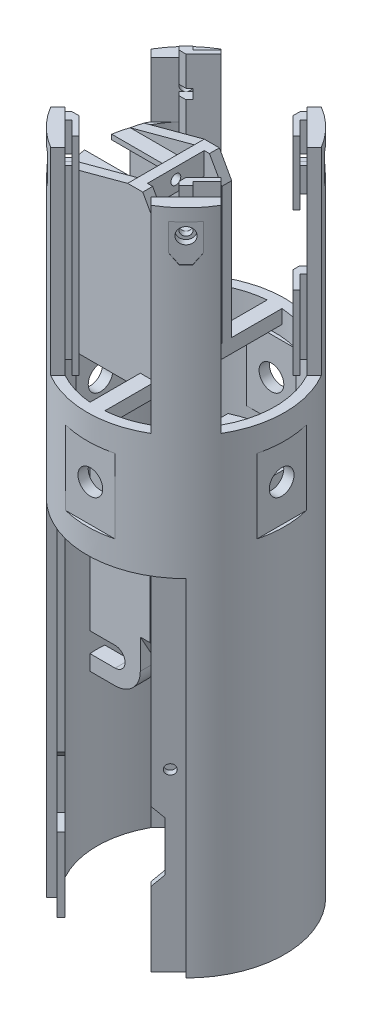
SolidWorks part; units mm, degrees
ref_plane "前视基准面" through (0, 0, 0) normal (0, 0, 1) x (1, 0, 0)
ref_plane "上视基准面" through (0, 0, 0) normal (0, 1, 0) x (1, 0, 0)
ref_plane "右视基准面" through (0, 0, 0) normal (1, 0, 0) x (0, 0, -1)
other "Configuration Table"
sketch "草图1" plane through (0, 0, 0) normal (0, 1, 0) x (1, 0, 0)
  circle A0 centre (0, 0) radius 20
  circle A1 centre (0, 0) radius 18
  dimension "D1" = 40
  dimension "D2" = 36
extrude "凸台-拉伸1" add sketch "草图1" along normal blind 25
sketch "草图2" plane through (0, 0, 0) normal (0, 1, 0) x (1, 0, 0)
  line L0 (-1000, 0) -> (49000, 0) construction
  line L1 (-17.9374, 1.5) -> (-17.9374, -1.5) construction
  line L2 (-17.9374, 1.5) -> (17.9374, 1.5)
  line L3 (-17.9374, -1.5) -> (17.9374, -1.5)
  circle A0 centre (0, 0) radius 18 construction
  arc A2 (-17.9374, 1.5) -> (-17.9374, -1.5) centre (0, 0) ccw
  arc A3 (17.9374, -1.5) -> (17.9374, 1.5) centre (0, 0) ccw
  point P8 (-17.9374, 0)
  dimension "D1" = 3
extrude "凸台-拉伸2" add sketch "草图2" along normal blind 2.8 from surface starting at face at (0, 0, 20)
sketch "草图3" plane through (0, 0, 0) normal (0, 1, 0) x (1, 0, 0)
  line L0 (0, -1000) -> (0, 49000) construction
  line L2 (7.75, 16.2462) -> (7.75, -1.5)
  line L3 (17.9374, -1.5) -> (-17.9374, -1.5) construction
  line L4 (7.75, -1.5) -> (-7.75, -1.5)
  line L5 (-7.75, -1.5) -> (-7.75, 16.2462)
  arc A0 (7.75, 16.2462) -> (-7.75, 16.2462) centre (0, 0) ccw
  point P9 (0, 16.2462)
  dimension "D1" = 15.5
  dimension "D2" = 15.5
  dimension "D3" = 17.7462
extrude "凸台-拉伸3" add sketch "草图3" along normal up to surface (2.8 mm away) up to face at (0, 2.8, 0)
sketch "草图4" plane through (0, 0, 0) normal (0, 1, 0) x (1, 0, 0)
  line L0 (7.75, 16.2462) -> (7.75, 2.0569)
  line L1 (-7.75, 16.2462) -> (-7.75, 2.0569)
  line L2 (5.75, 17.0569) -> (5.75, 4.0569)
  line L3 (-5.75, 17.0569) -> (-5.75, 4.0569)
  line L4 (5.75, 4.0569) -> (-5.75, 4.0569)
  line L5 (5.75, 2.0569) -> (-5.75, 2.0569)
  line L6 (-7.75, 2.0569) -> (-7.75, -1.5)
  line L7 (17.9374, -1.5) -> (-17.9374, -1.5) construction
  line L8 (-7.75, -1.5) -> (-5.75, -1.5)
  line L9 (-5.75, -1.5) -> (-5.75, 2.0569)
  line L10 (5.75, 2.0569) -> (5.75, -1.5)
  line L11 (5.75, -1.5) -> (7.75, -1.5)
  line L12 (7.75, -1.5) -> (7.75, 2.0569)
  arc A0 (7.75, 16.2462) -> (5.75, 17.0569) centre (0, 0) ccw
  arc A1 (-5.75, 17.0569) -> (-7.75, 16.2462) centre (0, 0) ccw
  dimension "D1" = 2
  dimension "D2" = 2
  dimension "D3" = 13
  dimension "D4" = 2
extrude "凸台-拉伸4" add sketch "草图4" against normal blind 32 from surface starting at face at (-11.8011, 0, -6.8681)
sketch "草图5" plane through (0, 0, 0) normal (0, 0, 1) x (1, 0, 0)
  line L0 (5.75, 0) -> (-5.75, -32) construction
  line L1 (5.75, -32) -> (-5.75, 0) construction
  line L2 (0, -2.2) -> (0, -29.8) construction
  line L3 (-5.75, -4.5) -> (5.75, -4.5)
  line L4 (-5.75, -4.5) -> (-5.75, -27.5)
  line L5 (-5.75, -27.5) -> (5.75, -27.5)
  line L6 (5.75, -4.5) -> (5.75, -27.5)
  line L7 (-5.75, -4.5) -> (5.75, -27.5) construction
  line L8 (-5.75, -27.5) -> (5.75, -4.5) construction
  circle A0 centre (0, -2.2) radius 1
  circle A1 centre (0, -29.8) radius 1
  point P8 (0, -16)
  point P17 (0, -16)
  dimension "D4" = 2
  dimension "D5" = 2
  dimension "D1" = 23
  dimension "D2" = 11.5
  dimension "D3" = 27.6
extrude "切除-拉伸1" cut sketch "草图5" against normal blind 32
sketch "草图6" plane through (0, 0, 0) normal (0, 1, 0) x (1, 0, 0)
  line L0 (5.75, 17.0569) -> (5.75, 4.0569)
  line L1 (-5.75, 4.0569) -> (5.75, 4.0569) construction
  line L2 (5.75, 4.0569) -> (5.75, 17.0569) construction
  line L3 (2.75, 4.0569) -> (2.75, 17.7887)
  line L4 (-5.75, 17.0569) -> (-5.75, 4.0569)
  line L5 (-5.75, 4.0569) -> (5.75, 4.0569) construction
  line L6 (-2.75, 4.0569) -> (-2.75, 17.7887)
  line L7 (2.75, 4.0569) -> (5.75, 4.0569)
  line L8 (-5.75, 4.0569) -> (-2.75, 4.0569)
  arc A0 (5.75, 17.0569) -> (2.75, 17.7887) centre (0, 0) ccw
  arc A1 (-2.75, 17.7887) -> (-5.75, 17.0569) centre (0, 0) ccw
  dimension "D1" = 3
  dimension "D2" = 3
extrude "凸台-拉伸5" add sketch "草图6" against normal blind 1 from surface starting at face at (0, -27.5, -3.0569)
sketch "草图7" plane through (0, 0, 0) normal (0, 1, 0) x (1, 0, 0)
  line L3 (2.75, 17.7887) -> (2.75, 4.0569)
  line L4 (5.75, 4.0569) -> (5.75, 17.0569)
  line L5 (2.75, 4.0569) -> (5.75, 4.0569)
  line L6 (2.75, 17.7887) -> (2.75, 4.0569)
  line L7 (5.75, 4.0569) -> (5.75, 17.0569)
  line L8 (2.75, 4.0569) -> (5.75, 4.0569)
  line L9 (-5.75, 17.0569) -> (-5.75, 4.0569)
  line L10 (-2.75, 4.0569) -> (-2.75, 17.7887)
  line L11 (-5.75, 4.0569) -> (-2.75, 4.0569)
  line L12 (-5.75, 17.0569) -> (-5.75, 4.0569)
  line L13 (-2.75, 4.0569) -> (-2.75, 17.7887)
  line L14 (-5.75, 4.0569) -> (-2.75, 4.0569)
  arc A1 (5.75, 17.0569) -> (2.75, 17.7887) centre (0, 0) ccw
  arc A2 (5.75, 17.0569) -> (2.75, 17.7887) centre (0, 0) ccw
  arc A3 (-2.75, 17.7887) -> (-5.75, 17.0569) centre (0, 0) ccw
  arc A4 (-2.75, 17.7887) -> (-5.75, 17.0569) centre (0, 0) ccw
  dimension "D1" = 0
  dimension "D2" = 0
extrude "凸台-拉伸6" add sketch "草图7" along normal blind 1 from surface starting at face at (0, -4.5, -3.0569)
sketch "草图8" plane through (0, 0, 0) normal (0, 1, 0) x (1, 0, 0)
  line L0 (-2.75, 17.7887) -> (-2.75, 4.0569) construction
  line L1 (2.75, 4.0569) -> (2.75, 17.7887) construction
  line L2 (-2.75, 17.7887) -> (-2.75, 4.0569)
  line L3 (2.75, 4.0569) -> (2.75, 17.7887)
  line L4 (2.75, 4.0569) -> (-2.75, 4.0569)
  arc A0 (2.75, 17.7887) -> (-2.75, 17.7887) centre (0, 0) ccw
extrude "切除-拉伸2" cut sketch "草图8" along normal up to surface (2.8 mm away) from surface up to face at (0, 2.8, -4.6558) starting at face at (0, 0, -0.2784)
sketch "草图9" plane through (0, 0, 0) normal (1, 0, 0) x (0, 0, -1)
  line L0 (-1.5, -32) -> (-1.5, -27.5)
  line L1 (-1.5, -32) -> (-1.5, 0) construction
  line L2 (-1.5, -32) -> (1, -32)
  line L3 (-1.5, -32) -> (16.2462, -32) construction
  line L4 (1, -32) -> (-1.5, -27.5)
  line L5 (17.0569, -32) -> (4.0569, -32)
  line L6 (4.0569, -32) -> (17.0569, -28.5)
  line L7 (17.0569, -28.5) -> (17.0569, -32)
  dimension "D1" = 4.5
  dimension "D2" = 13
  dimension "D3" = 2.5
extrude "切除-拉伸3" cut sketch "草图9" against normal through all and the other way through all contours L7 L5 L6 | L4 L0 L2
sketch "草图10" plane through (0, 0, 0) normal (0, 1, 0) x (1, 0, 0)
  line L0 (0, -1000) -> (0, 49000) construction
  line L1 (-1.5, 17.9374) -> (1.5, 17.9374) construction
  line L2 (-1.5, 17.9374) -> (-1.5, -17.9374)
  line L3 (1.5, 17.9374) -> (1.5, -17.9374)
  arc A0 (1.5, 17.9374) -> (-1.5, 17.9374) centre (0, 0) ccw
  arc A1 (-1.5, -17.9374) -> (1.5, -17.9374) centre (0, 0) ccw
  point P9 (0, 17.9374)
  dimension "D1" = 3
extrude "凸台-拉伸7" add sketch "草图10" against normal blind 2.8 from surface starting at face at (0, 25, 20)
sketch "草图12" plane through (0, 0, 0) normal (0, 1, 0) x (1, 0, 0)
  line L0 (-1000, 0) -> (49000, 0) construction
  line L1 (-16.2462, -7.75) -> (-16.2462, 7.75) construction
  line L2 (-16.2462, 7.75) -> (1.5, 7.75)
  line L3 (1.5, 17.9374) -> (1.5, -17.9374) construction
  line L4 (1.5, 7.75) -> (1.5, -7.75)
  line L5 (1.5, -7.75) -> (-16.2462, -7.75)
  arc A0 (-16.2462, 7.75) -> (-16.2462, -7.75) centre (0, 0) ccw
  point P9 (-16.2462, 0)
  dimension "D1" = 15.5
extrude "凸台-拉伸8" add sketch "草图12" against normal up to surface (-22.2 mm away) from surface up to face at (0, 22.2, 0) starting at face at (9.75, 25, 0)
sketch "草图13" plane through (0, 0, 0) normal (0, 1, 0) x (1, 0, 0)
  line L0 (-1000, 0) -> (49000, 0) construction
  line L1 (-16.2462, 7.75) -> (-16.2462, -7.75) construction
  line L2 (-16.2462, 7.75) -> (1.5, 7.75)
  line L3 (1.5, 17.9374) -> (1.5, -17.9374) construction
  line L4 (1.5, 7.75) -> (1.5, 5.75)
  line L5 (1.5, 5.75) -> (-2.0569, 5.75)
  line L6 (-16.2462, -7.75) -> (1.5, -7.75)
  line L7 (1.5, -7.75) -> (1.5, -5.75)
  line L8 (1.5, -5.75) -> (-2.0569, -5.75)
  line L9 (-4.0569, 5.75) -> (-4.0569, -5.75)
  line L10 (-2.0569, 5.75) -> (-2.0569, -5.75)
  line L11 (-4.0569, 5.75) -> (-17.0569, 5.75)
  line L12 (-4.0569, -5.75) -> (-17.0569, -5.75)
  arc A0 (-16.2462, 7.75) -> (-17.0569, 5.75) centre (0, 0) ccw
  arc A1 (-17.0569, -5.75) -> (-16.2462, -7.75) centre (0, 0) ccw
  point P9 (-16.2462, 0)
  point P18 (-7.3731, 7.75)
  dimension "D1" = 15.5
  dimension "D2" = 2
  dimension "D3" = 2
  dimension "D4" = 2
  dimension "D5" = 13
extrude "凸台-拉伸9" add sketch "草图13" along normal blind 32 from surface starting at face at (9.75, 25, 0)
sketch "草图14" plane through (0, 0, 0) normal (1, 0, 0) x (0, 0, -1)
  line L0 (5.75, 57) -> (-5.75, 25) construction
  line L1 (5.75, 25) -> (-5.75, 57) construction
  line L2 (0, 54.8) -> (0, 27.2) construction
  line L3 (-5.75, 52.5) -> (5.75, 52.5)
  line L4 (-5.75, 52.5) -> (-5.75, 29.5)
  line L5 (-5.75, 29.5) -> (5.75, 29.5)
  line L6 (5.75, 52.5) -> (5.75, 29.5)
  line L7 (-5.75, 52.5) -> (5.75, 29.5) construction
  line L8 (-5.75, 29.5) -> (5.75, 52.5) construction
  circle A0 centre (0, 54.8) radius 1
  circle A1 centre (0, 27.2) radius 1
  point P8 (0, 41)
  point P17 (0, 41)
  dimension "D4" = 2
  dimension "D5" = 2
  dimension "D1" = 23
  dimension "D2" = 11.5
  dimension "D3" = 27.6
extrude "切除-拉伸4" cut sketch "草图14" against normal blind 32
sketch "草图15" plane through (0, 0, 0) normal (0, 1, 0) x (1, 0, 0)
  line L0 (-17.0569, 5.75) -> (-4.0569, 5.75)
  line L1 (-4.0569, -5.75) -> (-4.0569, 5.75) construction
  line L2 (-4.0569, -5.75) -> (-4.0569, 5.75) construction
  line L3 (-4.0569, 5.75) -> (-4.0569, 2.75)
  line L4 (-4.0569, 2.75) -> (-17.7887, 2.75)
  line L5 (-4.0569, -5.75) -> (-4.0569, -2.75)
  line L6 (-4.0569, -2.75) -> (-17.7887, -2.75)
  line L7 (-4.0569, -5.75) -> (-17.0569, -5.75)
  line L8 (-17.0569, -5.75) -> (-4.0569, -5.75) construction
  arc A0 (-17.7887, -2.75) -> (-17.0569, -5.75) centre (0, 0) ccw
  arc A1 (-17.0569, 5.75) -> (-17.7887, 2.75) centre (0, 0) ccw
  dimension "D1" = 3
  dimension "D2" = 3
extrude "凸台-拉伸10" add sketch "草图15" against normal blind 1 from surface starting at face at (-3.0569, 29.5, 0)
sketch "草图16" plane through (0, 0, 0) normal (0, 1, 0) x (1, 0, 0)
  line L0 (-4.0569, 5.75) -> (-4.0569, 2.75)
  line L1 (-4.0569, -2.75) -> (-4.0569, -5.75)
  line L2 (-17.0569, -5.75) -> (-2.0569, -5.75) construction
  line L3 (-4.0569, -5.75) -> (-4.0569, 5.75) construction
  line L4 (-17.7887, 2.75) -> (-4.0569, 2.75) construction
  line L5 (-17.7887, 2.75) -> (-4.0569, 2.75)
  line L6 (-4.0569, -2.75) -> (-17.7887, -2.75) construction
  line L7 (-4.0569, -2.75) -> (-17.7887, -2.75)
  line L8 (-4.0569, 5.75) -> (-17.0569, 5.75)
  line L9 (-4.0569, -5.75) -> (-17.0569, -5.75)
  arc A0 (-17.7887, -2.75) -> (-17.0569, -5.75) centre (0, 0) ccw construction
  arc A1 (-17.7887, -2.75) -> (-17.0569, -5.75) centre (0, 0) ccw
  arc A2 (-17.0569, 5.75) -> (-17.7887, 2.75) centre (0, 0) ccw construction
  arc A3 (-17.0569, 5.75) -> (-17.7887, 2.75) centre (0, 0) ccw
extrude "凸台-拉伸11" add sketch "草图16" along normal blind 1 from surface contours L8 A3 L5 L0 | L7 A1 L9 L1 region at (-10.7643, 0, -4.2364) region at (-10.7643, 0, 4.2364) starting at face at (-3.0569, 52.5, 0)
sketch "草图17" plane through (0, 0, 0) normal (0, 1, 0) x (1, 0, 0)
  line L0 (-4.0569, -5.75) -> (-4.0569, 5.75) construction
  line L1 (-17.7887, -2.75) -> (-4.0569, -2.75) construction
  line L2 (-4.0569, 2.75) -> (-17.7887, 2.75) construction
  line L3 (-4.0569, -2.75) -> (-4.0569, 2.75)
  line L4 (-17.7887, -2.75) -> (-4.0569, -2.75)
  line L5 (-4.0569, 2.75) -> (-17.7887, 2.75)
  arc A0 (-17.7887, 2.75) -> (-17.7887, -2.75) centre (0, 0) ccw
extrude "切除-拉伸5" cut sketch "草图17" against normal up to surface (-22.2 mm away) from surface up to face at (-4.6558, 22.2, 0) starting at face at (0, 25, 20)
sketch "草图18" plane through (0, 0, 0) normal (0, 0, 1) x (1, 0, 0)
  line L0 (1.5, 57) -> (1.5, 52.5)
  line L1 (1.5, 57) -> (1.5, 25) construction
  line L2 (1.5, 52.5) -> (-1, 57)
  line L3 (1.5, 57) -> (-16.2462, 57) construction
  line L4 (-1, 57) -> (1.5, 57)
  line L5 (-17.0569, 53.5) -> (-4.0569, 57)
  line L6 (-4.0569, 57) -> (-17.0569, 57)
  line L7 (-17.0569, 57) -> (-17.0569, 53.5)
  dimension "D1" = 13
  dimension "D2" = 4.5
  dimension "D3" = 2.5
extrude "切除-拉伸6" cut sketch "草图18" against normal through all and the other way through all
sketch "草图19" plane through (0, 0, 0) normal (0, 0, 1) x (1, 0, 0)
  line L0 (20, 25) -> (-20, 0) construction
  line L1 (-20, 25) -> (20, 0) construction
  circle A0 centre (0, 12.5) radius 2.5
  dimension "D1" = 5
sketch "草图20" plane through (0, 0, 0) normal (1, 0, 0) x (0, 0, -1)
  line L0 (20, 25) -> (-20, 0) construction
  line L1 (-20, 25) -> (20, 0) construction
  circle A0 centre (0, 12.5) radius 2.5
  dimension "D1" = 5
sketch "草图21" plane through (0, 0, 0) normal (0, 1, 0) x (1, 0, 0)
  line L0 (0, -1000) -> (0, 49000) construction
  line L1 (-1000, 0) -> (49000, 0) construction
  line L2 (-17.2916, -5) -> (-17.2916, 5)
  line L3 (17.2916, -5) -> (17.2916, 5)
  line L4 (-5, 17.2916) -> (5, 17.2916)
  line L5 (-5, -17.2916) -> (5, -17.2916)
  arc A0 (-17.2916, 5) -> (-17.2916, -5) centre (0, 0) ccw
  arc A1 (17.2916, -5) -> (17.2916, 5) centre (0, 0) ccw
  arc A2 (5, 17.2916) -> (-5, 17.2916) centre (0, 0) ccw
  arc A3 (-5, -17.2916) -> (5, -17.2916) centre (0, 0) ccw
  point P11 (-17.2916, 0)
  point P16 (0, 17.2916)
  dimension "D1" = 10
  dimension "D2" = 10
extrude "凸台-拉伸12" add sketch "草图21" along normal blind 15 from offset 5
sketch "草图22" plane through (0, 0, 0) normal (0, 1, 0) x (1, 0, 0)
  line L0 (-1000, 0) -> (49000, 0) construction
  line L1 (0, -1000) -> (0, 49000) construction
  line L2 (-5, 19.3649) -> (5, 19.3649)
  line L3 (-19.3649, -5) -> (-19.3649, 5)
  line L4 (19.3649, -5) -> (19.3649, 5)
  line L5 (-5, -19.3649) -> (5, -19.3649)
  arc A0 (-19.3649, 5) -> (-19.3649, -5) centre (0, 0) ccw
  arc A1 (5, 19.3649) -> (-5, 19.3649) centre (0, 0) ccw
  arc A2 (19.3649, -5) -> (19.3649, 5) centre (0, 0) ccw
  arc A3 (-5, -19.3649) -> (5, -19.3649) centre (0, 0) ccw
  point P10 (0, 19.3649)
  point P13 (-19.3649, 0)
  dimension "D1" = 40
  dimension "D2" = 10
  dimension "D3" = 10
extrude "切除-拉伸9" cut sketch "草图22" along normal blind 15 from offset 5
extrude "切除-拉伸10" cut sketch "草图19" against normal through all and the other way through all
extrude "切除-拉伸11" cut sketch "草图20" against normal through all and the other way through all
sketch "草图24" plane through (0, 0, 0) normal (0, 1, 0) x (1, 0, 0)
  circle A0 centre (0, 0) radius 20
  circle A1 centre (0, 0) radius 18
  dimension "D1" = 40
extrude "凸台-拉伸14" add sketch "草图24" against normal blind 70
sketch "草图27" plane through (0, 0, 0) normal (0, 1, 0) x (1, 0, 0)
  line L0 (-707.1068, -707.1068) -> (34648.2323, 34648.2323) construction
  line L1 (707.1068, -707.1068) -> (-34648.2323, 34648.2323) construction
  line L2 (-14.1421, -14.1421) -> (-12.7279, -12.7279)
  line L3 (14.1421, -14.1421) -> (12.7279, -12.7279)
  line L4 (-12.7279, 12.7279) -> (-14.1421, 14.1421)
  line L5 (12.7279, 12.7279) -> (14.1421, 14.1421)
  circle A0 centre (0, 0) radius 20 construction
  arc A1 (-14.1421, -14.1421) -> (14.1421, -14.1421) centre (0, 0) ccw
  circle A2 centre (0, 0) radius 18 construction
  arc A3 (-12.7279, -12.7279) -> (12.7279, -12.7279) centre (0, 0) ccw
  arc A4 (14.1421, 14.1421) -> (-14.1421, 14.1421) centre (0, 0) ccw
  arc A5 (12.7279, 12.7279) -> (-12.7279, 12.7279) centre (0, 0) ccw
extrude "切除-拉伸13" cut sketch "草图27" along normal up to surface from surface up to face at (0, 0, -0.2784) starting at face at (0, -70, 18)
sketch "草图28" plane through (0, 0, 0) normal (0, 1, 0) x (1, 0, 0)
  line L3 (-7.75, 1.5) -> (-17.9374, 1.5)
  line L4 (-7.75, -1.5) -> (-7.75, 1.5)
  line L5 (-17.9374, -1.5) -> (-7.75, -1.5)
  line L6 (-7.75, 1.5) -> (-17.9374, 1.5)
  line L7 (-7.75, -1.5) -> (-7.75, 1.5)
  line L8 (-17.9374, -1.5) -> (-7.75, -1.5)
  line L9 (7.75, -1.5) -> (17.9374, -1.5)
  line L10 (7.75, 1.5) -> (7.75, -1.5)
  line L11 (17.9374, 1.5) -> (7.75, 1.5)
  line L12 (7.75, -1.5) -> (17.9374, -1.5)
  line L13 (7.75, 1.5) -> (7.75, -1.5)
  line L14 (17.9374, 1.5) -> (7.75, 1.5)
  arc A0 (-12.7279, 12.7279) -> (-12.7279, -12.7279) centre (0, 0) ccw construction
  arc A1 (-17.9374, 1.5) -> (-17.9374, -1.5) centre (0, 0) ccw
  arc A2 (-17.9374, 1.5) -> (-17.9374, -1.5) centre (0, 0) ccw
  arc A3 (-17.9374, 1.5) -> (-17.9374, -1.5) centre (0, 0) ccw
  arc A4 (12.7279, -12.7279) -> (12.7279, 12.7279) centre (0, 0) ccw construction
  arc A5 (17.9374, -1.5) -> (17.9374, 1.5) centre (0, 0) ccw
  arc A7 (17.9374, -1.5) -> (17.9374, 1.5) centre (0, 0) ccw
  arc A8 (17.9374, -1.5) -> (17.9374, 1.5) centre (0, 0) ccw
  dimension "D1" = 0
  dimension "D2" = 0
extrude "凸台-拉伸16" add sketch "草图28" against normal up to vertex (27.5 mm away) contours L12 A5 L14 L13 | L6 A2 L8 L7 region at (-12.8646, 0, 0) region at (12.8646, 0, 0) up to point (-7.75, -27.5, 1.5)
sketch "草图32" plane through (0, 0, 0) normal (0, 1, 0) x (1, 0, 0)
  line L0 (-1000, 0) -> (49000, 0) construction
  line L1 (0, -1000) -> (0, 49000) construction
  line L2 (-707.1068, -707.1068) -> (34648.2323, 34648.2323) construction
  line L3 (707.1068, -707.1068) -> (-34648.2323, 34648.2323) construction
  line L4 (-15.7626, -8.6915) -> (-8.6915, -15.7626)
  line L8 (16.6111, -9.54) -> (9.54, -16.6111)
  line L9 (-16.6111, -9.54) -> (-9.54, -16.6111)
  line L10 (-16.6111, -9.54) -> (-15.7626, -8.6915)
  line L11 (-9.54, -16.6111) -> (-8.6915, -15.7626)
  line L12 (16.6111, -9.54) -> (15.7626, -8.6915)
  line L13 (15.7626, -8.6915) -> (8.6915, -15.7626)
  line L14 (9.54, -16.6111) -> (8.6915, -15.7626)
  line L15 (16.6111, 9.54) -> (15.7626, 8.6915)
  line L16 (15.7626, 8.6915) -> (8.6915, 15.7626)
  line L17 (9.54, 16.6111) -> (8.6915, 15.7626)
  line L18 (16.6111, 9.54) -> (9.54, 16.6111)
  line L19 (-16.6111, 9.54) -> (-9.54, 16.6111)
  line L20 (-16.6111, 9.54) -> (-15.7626, 8.6915)
  line L21 (-15.7626, 8.6915) -> (-8.6915, 15.7626)
  line L22 (-9.54, 16.6111) -> (-8.6915, 15.7626)
  circle A0 centre (0, 0) radius 18 construction
  point P15 (-12.227, -12.227)
  point P19 (-12.7279, -12.7279)
  point P22 (-13.0755, -13.0755)
  dimension "D1" = 10
  dimension "D2" = 10
  dimension "D3" = 1.2
extrude "凸台-拉伸30" add sketch "草图32" against normal up to surface (70 mm away) from surface contours L9 L11 L4 L10 | L19 L22 L21 L20 | L18 L17 L16 L15 | L8 L14 L13 L12 up to face at (-16.2175, -70, 0) starting at face at (0, 25, 20)
sketch "草图33" plane through (0, 0, 0) normal (0, 1, 0) x (1, 0, 0)
  line L0 (-15.7626, -8.6915) -> (-15.7626, -10.1915)
  line L1 (-15.7626, -10.1915) -> (-14.2626, -10.1915)
  line L2 (-15.7626, -8.6915) -> (-8.6915, -15.7626) construction
  line L3 (-14.2626, -10.1915) -> (-15.7626, -8.6915)
  line L4 (0, -1000) -> (0, 49000) construction
  line L5 (14.2626, -10.1915) -> (15.7626, -8.6915)
  line L6 (15.7626, -10.1915) -> (14.2626, -10.1915)
  line L7 (15.7626, -8.6915) -> (15.7626, -10.1915)
  dimension "D1" = 1.5
extrude "切除-拉伸14" cut sketch "草图33" against normal blind 10 from offset 17 offset against normal yes
ref_plane "基准面1" through (0, 0, 0) normal (-0.7071, 0, 0.7071) x (0, -1, 0)
sketch "草图36" plane through (0, 0, 0) normal (-0.7071, 0, 0.7071) x (0, -1, 0)
  line L0 (70, 5) -> (48, 5) construction
  line L1 (70, 5) -> (0, 5) construction
  line L2 (43, 5) -> (53, 5)
  line L4 (53, 3) -> (43, 3)
  line L6 (53, 3) -> (55, 5)
  line L7 (55, 5) -> (53, 5)
  line L8 (43, 3) -> (41, 5)
  line L9 (70, 5) -> (-25, 5) construction
  line L10 (41, 5) -> (43, 5)
  point P8 (48, 5)
  dimension "D1" = 22
  dimension "D2" = 10
  dimension "D3" = 2
  dimension "D4" = 45
  dimension "D5" = 10
  dimension "D6" = 2
extrude "切除-拉伸19" cut sketch "草图36" against normal up to next from surface contours L2 L7 L6 L4 L8 L10 starting at face at (-11.3078, -35, 14.8433)
sketch "草图38" plane through (0, 0, 0) normal (-0.7071, 0, 0.7071) x (0, -1, 0)
  line L0 (70, -5) -> (48, -5) construction
  line L1 (70, -5) -> (0, -5) construction
  line L2 (43, -5) -> (53, -5)
  line L4 (53, -3) -> (43, -3)
  line L6 (43, -3) -> (41, -5)
  line L7 (41, -5) -> (43, -5)
  line L8 (53, -3) -> (55, -5)
  line L9 (55, -5) -> (53, -5)
  point P7 (48, -5)
  dimension "D1" = 22
  dimension "D2" = 10
  dimension "D3" = 2
  dimension "D4" = 10
  dimension "D5" = 45
  dimension "D6" = 2
extrude "切除-拉伸20" cut sketch "草图38" against normal up to next from surface starting at face at (11.5199, -18, -12.9341)
ref_plane "基准面2" through (0, 0, 0) normal (-0.7071, 0, -0.7071) x (0, -1, 0)
sketch "草图39" plane through (0, 0, 0) normal (-0.7071, 0, -0.7071) x (0, -1, 0)
  line L0 (70, -5) -> (48, -5) construction
  line L1 (70, -5) -> (27, -5) construction
  line L2 (43, -5) -> (53, -5)
  line L4 (53, -3) -> (43, -3)
  line L6 (53, -3) -> (55, -5)
  line L7 (55, -5) -> (53, -5)
  line L8 (43, -3) -> (41, -5)
  line L9 (41, -5) -> (43, -5)
  point P8 (48, -5)
  dimension "D1" = 22
  dimension "D2" = 10
  dimension "D3" = 2
  dimension "D4" = 10
  dimension "D5" = 135
  dimension "D6" = 2
extrude "切除-拉伸21" cut sketch "草图39" against normal up to next from surface contours L4 L8 L9 L2 L7 L6 starting at face at (-11.3078, -35, -14.8433)
sketch "草图40" plane through (0, 0, 0) normal (-0.7071, 0, -0.7071) x (0, -1, 0)
  line L0 (70, 5) -> (48, 5) construction
  line L1 (70, 5) -> (0, 5) construction
  line L2 (43, 5) -> (53, 5)
  line L4 (53, 3) -> (43, 3)
  line L6 (53, 3) -> (55, 5)
  line L7 (55, 5) -> (53, 5)
  line L8 (43, 3) -> (41, 5)
  line L9 (41, 5) -> (43, 5)
  point P8 (48, 5)
  dimension "D1" = 22
  dimension "D2" = 10
  dimension "D3" = 2
  dimension "D4" = 10
  dimension "D5" = 45
  dimension "D6" = 2
extrude "切除-拉伸22" cut sketch "草图40" against normal up to next from surface starting at face at (13.0722, -19.7778, 11.3818)
sketch "草图41" plane through (0, 0, 0) normal (-0.7071, 0, 0.7071) x (0, -1, 0)
  line L0 (70, 5) -> (32, 5) construction
  line L1 (41, 5) -> (0, 5) construction
  line L2 (32, 5) -> (32, 0) construction
  line L3 (0, 0) -> (70, 0) construction
  circle A0 centre (34.5, 2.25) radius 1
  dimension "D2" = 2
  dimension "D4" = 2.5
  dimension "D1" = 38
  dimension "D3" = 2.75
extrude "切除-拉伸23" cut sketch "草图41" along normal up to next
sketch "草图45" plane through (0, 0, 0) normal (-0.7071, 0, 0.7071) x (0, -1, 0)
  line L0 (70, 0) -> (70, -5) construction
  line L1 (41, -5) -> (0, -5) construction
  circle A0 centre (34.5, -2.25) radius 1
  dimension "D2" = 2
  dimension "D1" = 35.5
  dimension "D3" = 2.75
extrude "切除-拉伸28" cut sketch "草图45" against normal up to next
sketch "草图46" plane through (0, 0, 0) normal (-0.7071, 0, -0.7071) x (0, -1, 0)
  line L0 (70, 0) -> (70, -5) construction
  line L1 (70, 0) -> (0, 0) construction
  circle A0 centre (34.5, -2.25) radius 1
  dimension "D2" = 2
  dimension "D1" = 35.5
  dimension "D3" = 2.25
extrude "切除-拉伸29" cut sketch "草图46" along normal up to next
sketch "草图47" plane through (0, 0, 0) normal (-0.7071, 0, -0.7071) x (0, -1, 0)
  line L0 (70, 0) -> (0, 0) construction
  line L1 (70, 0) -> (70, 5) construction
  circle A0 centre (34.5, 2.25) radius 1
  dimension "D1" = 2
  dimension "D3" = 35.5
  dimension "D2" = 2.25
extrude "切除-拉伸30" cut sketch "草图47" against normal up to next
sketch "草图48" plane through (0, 0, 0) normal (0, 1, 0) x (1, 0, 0)
  line L0 (-1000, 0) -> (49000, 0) construction
  line L1 (0, -1000) -> (0, 49000) construction
  line L2 (-707.1068, -707.1068) -> (34648.2323, 34648.2323) construction
  line L3 (707.1068, -707.1068) -> (-34648.2323, 34648.2323) construction
  line L4 (8.6915, -15.7626) -> (15.7626, -8.6915) construction
  line L5 (-8.6915, -15.7626) -> (-15.7626, -8.6915) construction
  line L6 (-8.6915, 15.7626) -> (-15.7626, 8.6915) construction
  line L7 (8.6915, 15.7626) -> (15.7626, 8.6915) construction
  line L8 (8.6915, -15.7626) -> (15.7626, -8.6915)
  line L9 (-8.6915, -15.7626) -> (-15.7626, -8.6915)
  line L10 (-8.6915, 15.7626) -> (-15.7626, 8.6915)
  line L11 (8.6915, 15.7626) -> (15.7626, 8.6915)
  line L12 (8.6915, 15.7626) -> (10.1575, 17.2286)
  line L14 (17.2286, 10.1575) -> (15.7626, 8.6915)
  line L15 (-8.6915, 15.7626) -> (-10.1575, 17.2286)
  line L17 (-17.2286, 10.1575) -> (-15.7626, 8.6915)
  line L20 (-10.1575, -17.2286) -> (-8.6915, -15.7626)
  line L21 (-15.7626, -8.6915) -> (-17.2286, -10.1575)
  line L22 (15.7626, -8.6915) -> (17.2286, -10.1575)
  line L24 (10.1575, -17.2286) -> (8.6915, -15.7626)
  circle A0 centre (0, 0) radius 18 construction
  arc A1 (10.1575, -17.2286) -> (17.2286, -10.1575) centre (0, 0) ccw
  arc A2 (-17.2286, -10.1575) -> (-10.1575, -17.2286) centre (0, 0) ccw
  arc A3 (-10.1575, 17.2286) -> (-17.2286, 10.1575) centre (0, 0) ccw
  arc A4 (17.2286, 10.1575) -> (10.1575, 17.2286) centre (0, 0) ccw
  dimension "D1" = 40
  dimension "D2" = 10
extrude "凸台-拉伸31" add sketch "草图48" along normal blind 40 from surface starting at face at (-4.4792, 25, 0)
sketch "草图49" plane through (0, 0, 0) normal (0, 1, 0) x (1, 0, 0)
  line L0 (-1000, 0) -> (49000, 0) construction
  line L1 (0, -1000) -> (0, 49000) construction
  line L2 (-707.1068, -707.1068) -> (34648.2323, 34648.2323) construction
  line L10 (707.1068, -707.1068) -> (-34648.2323, 34648.2323) construction
  line L16 (-15.7626, -8.6915) -> (-8.6915, -15.7626) construction
  line L27 (8.6915, -15.7626) -> (15.7626, -8.6915) construction
  line L28 (15.7626, 8.6915) -> (8.6915, 15.7626) construction
  line L29 (-8.6915, 15.7626) -> (-15.7626, 8.6915) construction
  line L30 (-12.9341, -11.5199) -> (-8.6915, -15.7626) construction
  line L31 (11.5199, -12.9341) -> (15.7626, -8.6915) construction
  line L32 (15.7626, 8.6915) -> (8.6915, 15.7626) construction
  line L33 (-8.6915, 15.7626) -> (-12.9341, 11.5199) construction
  line L34 (-12.9341, 11.5199) -> (-11.5199, 12.9341)
  line L35 (-11.5199, 12.9341) -> (-10.8128, 12.227)
  line L36 (-10.8128, 12.227) -> (-7.9844, 15.0554)
  line L37 (-7.9844, 15.0554) -> (-7.2773, 14.3483)
  line L38 (-7.2773, 14.3483) -> (-10.8128, 10.8128)
  line L41 (-12.227, 10.8128) -> (-12.9341, 11.5199)
  line L42 (14.3483, 7.2773) -> (15.0554, 7.9844)
  line L43 (10.8128, 10.8128) -> (14.3483, 7.2773)
  line L46 (15.0554, 7.9844) -> (12.227, 10.8128)
  line L47 (12.227, 10.8128) -> (12.9341, 11.5199)
  line L48 (12.9341, 11.5199) -> (11.5199, 12.9341)
  line L49 (11.5199, 12.9341) -> (10.8128, 12.227)
  line L52 (-7.2773, -14.3483) -> (-10.8128, -10.8128)
  line L53 (-7.9844, -15.0554) -> (-7.2773, -14.3483)
  line L54 (-10.8128, -12.227) -> (-7.9844, -15.0554)
  line L55 (-11.5199, -12.9341) -> (-10.8128, -12.227)
  line L56 (-12.9341, -11.5199) -> (-11.5199, -12.9341)
  line L57 (-12.227, -10.8128) -> (-12.9341, -11.5199)
  line L58 (10.8128, -10.8128) -> (14.3483, -7.2773)
  line L61 (11.5199, -12.9341) -> (10.8128, -12.227)
  line L62 (12.9341, -11.5199) -> (11.5199, -12.9341)
  line L63 (12.227, -10.8128) -> (12.9341, -11.5199)
  line L64 (15.0554, -7.9844) -> (12.227, -10.8128)
  line L65 (14.3483, -7.2773) -> (15.0554, -7.9844)
  line L66 (-12.227, -10.8128) -> (-10.8128, -10.8128)
  line L67 (-12.227, 10.8128) -> (-10.8128, 10.8128)
  line L68 (10.8128, -12.227) -> (10.8128, -10.8128)
  line L69 (10.8128, 12.227) -> (10.8128, 10.8128)
  point P19 (-12.227, 12.227)
  dimension "D1" = 1
  dimension "D2" = 1
  dimension "D3" = 2
  dimension "D4" = 4
  dimension "D5" = 135
  dimension "D6" = 135
  dimension "D7" = 135
  dimension "D8" = 4
  dimension "D9" = 135
extrude "凸台-拉伸32" add sketch "草图49" along normal up to surface (40 mm away) from surface up to face at (-13.0723, 65, 13.0723) starting at face at (0, 25, 15.1109)
sketch "草图51" plane through (0, 0, 0) normal (0, 1, 0) x (1, 0, 0)
  line L0 (12.9341, -11.5199) -> (11.5199, -12.9341)
  line L1 (11.5199, 12.9341) -> (12.9341, 11.5199)
  line L10 (15.7626, 8.6915) -> (17.2286, 10.1575)
  line L11 (10.1575, 17.2286) -> (8.6915, 15.7626)
  line L12 (8.6915, 15.7626) -> (11.5199, 12.9341)
  line L13 (11.5199, 12.9341) -> (10.8128, 12.227)
  line L14 (10.8128, 12.227) -> (10.8128, 10.8128)
  line L15 (10.8128, 10.8128) -> (14.3483, 7.2773)
  line L16 (14.3483, 7.2773) -> (15.0554, 7.9844)
  line L17 (15.0554, 7.9844) -> (12.227, 10.8128)
  line L18 (12.227, 10.8128) -> (12.9341, 11.5199)
  line L19 (12.9341, 11.5199) -> (15.7626, 8.6915)
  line L23 (11.5199, 12.9341) -> (10.8128, 12.227)
  line L24 (10.8128, 12.227) -> (10.8128, 10.8128)
  line L25 (10.8128, 10.8128) -> (14.3483, 7.2773)
  line L26 (14.3483, 7.2773) -> (15.0554, 7.9844)
  line L27 (15.0554, 7.9844) -> (12.227, 10.8128)
  line L28 (12.227, 10.8128) -> (12.9341, 11.5199)
  line L30 (17.2286, -10.1575) -> (15.7626, -8.6915)
  line L31 (15.7626, -8.6915) -> (12.9341, -11.5199)
  line L32 (12.9341, -11.5199) -> (12.227, -10.8128)
  line L33 (12.227, -10.8128) -> (15.0554, -7.9844)
  line L34 (15.0554, -7.9844) -> (14.3483, -7.2773)
  line L35 (14.3483, -7.2773) -> (10.8128, -10.8128)
  line L36 (10.8128, -10.8128) -> (10.8128, -12.227)
  line L37 (10.8128, -12.227) -> (11.5199, -12.9341)
  line L38 (11.5199, -12.9341) -> (8.6915, -15.7626)
  line L39 (8.6915, -15.7626) -> (10.1575, -17.2286)
  line L42 (12.9341, -11.5199) -> (12.227, -10.8128)
  line L43 (12.227, -10.8128) -> (15.0554, -7.9844)
  line L44 (15.0554, -7.9844) -> (14.3483, -7.2773)
  line L45 (14.3483, -7.2773) -> (10.8128, -10.8128)
  line L46 (10.8128, -10.8128) -> (10.8128, -12.227)
  line L47 (10.8128, -12.227) -> (11.5199, -12.9341)
  arc A1 (17.2286, 10.1575) -> (10.1575, 17.2286) centre (0, 0) ccw
  arc A3 (10.1575, -17.2286) -> (17.2286, -10.1575) centre (0, 0) ccw
  dimension "D1" = 0
  dimension "D2" = 0
extrude "切除-拉伸31" cut sketch "草图51" against normal blind 25 from surface starting at face at (-11.4416, 65, 12.7272)
sketch "草图52" plane through (0, 0, 0) normal (0, 1, 0) x (1, 0, 0)
  line L0 (8.6915, 15.7626) -> (9.4245, 16.4956)
  line L1 (8.6915, 15.7626) -> (10.1575, 17.2286) construction
  line L5 (10.1575, -17.2286) -> (8.6915, -15.7626) construction
  line L7 (8.6915, -15.7626) -> (9.4245, -16.4956)
  line L8 (9.4245, 16.4956) -> (11.5199, 12.9341)
  line L9 (11.5199, 12.9341) -> (8.6915, 15.7626)
  line L10 (9.4245, -16.4956) -> (11.5199, -12.9341)
  line L11 (11.5199, -12.9341) -> (8.6915, -15.7626)
extrude "切除-拉伸32" cut sketch "草图52" along normal blind 5 and the other way blind 5 from offset 47
sketch "草图58" plane through (0, 0, 0) normal (0, 1, 0) x (1, 0, 0)
  line L0 (-12.9341, 11.5199) -> (-15.7626, 8.6915)
  line L1 (-16.2462, 7.75) -> (-15.4899, 7.75)
  line L2 (-16.2462, -7.75) -> (-15.4899, -7.75)
  line L3 (-4.0569, -7.75) -> (-16.2462, -7.75) construction
  line L4 (-12.9341, -11.5199) -> (-15.7626, -8.6915)
  arc A0 (-15.7626, 8.6915) -> (-16.2462, 7.75) centre (0, 0) ccw
  arc A1 (-12.9341, 11.5199) -> (-15.4899, 7.75) centre (0, 0) ccw
  arc A2 (-15.4899, -7.75) -> (-12.9341, -11.5199) centre (0, 0) ccw
  arc A3 (-16.2462, -7.75) -> (-15.7626, -8.6915) centre (0, 0) ccw
extrude "凸台-拉伸40" add sketch "草图58" along normal up to vertex and the other way blind 0.25 from surface up to point (-16.2462, 53.7183, -7.75) starting at face at (0, 25, 15.1109)
sketch "草图59" plane through (0, 0, 0) normal (0, 1, 0) x (1, 0, 0)
  line L0 (-11.5199, 12.9341) -> (-12.9341, 11.5199)
  line L1 (-12.9341, -11.5199) -> (-11.5199, -12.9341)
  line L10 (-15.7626, -8.6915) -> (-17.2286, -10.1575)
  line L11 (-10.1575, -17.2286) -> (-8.6915, -15.7626)
  line L12 (-8.6915, -15.7626) -> (-11.5199, -12.9341)
  line L13 (-11.5199, -12.9341) -> (-10.8128, -12.227)
  line L14 (-10.8128, -12.227) -> (-7.9844, -15.0554)
  line L15 (-7.9844, -15.0554) -> (-7.2773, -14.3483)
  line L16 (-7.2773, -14.3483) -> (-10.8128, -10.8128)
  line L17 (-10.8128, -10.8128) -> (-12.227, -10.8128)
  line L18 (-12.227, -10.8128) -> (-12.9341, -11.5199)
  line L19 (-12.9341, -11.5199) -> (-15.7626, -8.6915)
  line L23 (-11.5199, -12.9341) -> (-10.8128, -12.227)
  line L24 (-10.8128, -12.227) -> (-7.9844, -15.0554)
  line L25 (-7.9844, -15.0554) -> (-7.2773, -14.3483)
  line L26 (-7.2773, -14.3483) -> (-10.8128, -10.8128)
  line L27 (-10.8128, -10.8128) -> (-12.227, -10.8128)
  line L28 (-12.227, -10.8128) -> (-12.9341, -11.5199)
  line L30 (-17.2286, 10.1575) -> (-15.7626, 8.6915)
  line L31 (-15.7626, 8.6915) -> (-12.9341, 11.5199)
  line L32 (-12.9341, 11.5199) -> (-12.227, 10.8128)
  line L33 (-12.227, 10.8128) -> (-10.8128, 10.8128)
  line L34 (-10.8128, 10.8128) -> (-7.2773, 14.3483)
  line L35 (-7.2773, 14.3483) -> (-7.9844, 15.0554)
  line L36 (-7.9844, 15.0554) -> (-10.8128, 12.227)
  line L37 (-10.8128, 12.227) -> (-11.5199, 12.9341)
  line L38 (-11.5199, 12.9341) -> (-8.6915, 15.7626)
  line L39 (-8.6915, 15.7626) -> (-10.1575, 17.2286)
  line L42 (-12.9341, 11.5199) -> (-12.227, 10.8128)
  line L43 (-12.227, 10.8128) -> (-10.8128, 10.8128)
  line L44 (-10.8128, 10.8128) -> (-7.2773, 14.3483)
  line L45 (-7.2773, 14.3483) -> (-7.9844, 15.0554)
  line L46 (-7.9844, 15.0554) -> (-10.8128, 12.227)
  line L47 (-10.8128, 12.227) -> (-11.5199, 12.9341)
  arc A1 (-17.2286, -10.1575) -> (-10.1575, -17.2286) centre (0, 0) ccw
  arc A3 (-10.1575, 17.2286) -> (-17.2286, 10.1575) centre (0, 0) ccw
  dimension "D1" = 0
  dimension "D2" = 0
extrude "凸台-拉伸41" add sketch "草图59" along normal blind 2 from surface contours L0 L42 L43 L44 L45 L46 L47 | L23 L24 L25 L26 L27 L28 L1 starting at face at (-11.4416, 65, 12.7272)
sketch "草图60" plane through (0, 0, 0) normal (0, 1, 0) x (1, 0, 0)
  line L0 (10.8128, -10.8128) -> (10.8128, -12.227) construction
  line L1 (10.8128, -12.227) -> (11.5199, -12.9341) construction
  line L2 (11.5199, -12.9341) -> (12.9341, -11.5199) construction
  line L3 (12.9341, -11.5199) -> (12.227, -10.8128) construction
  line L4 (12.227, -10.8128) -> (15.0554, -7.9844) construction
  line L5 (15.0554, -7.9844) -> (14.3483, -7.2773) construction
  line L6 (14.3483, -7.2773) -> (10.8128, -10.8128) construction
  line L7 (15.0554, 7.9844) -> (12.227, 10.8128) construction
  line L8 (12.227, 10.8128) -> (12.9341, 11.5199) construction
  line L9 (12.9341, 11.5199) -> (11.5199, 12.9341) construction
  line L10 (11.5199, 12.9341) -> (10.8128, 12.227) construction
  line L11 (10.8128, 12.227) -> (10.8128, 10.8128) construction
  line L12 (10.8128, 10.8128) -> (14.3483, 7.2773) construction
  line L13 (14.3483, 7.2773) -> (15.0554, 7.9844) construction
  line L14 (10.8128, -10.8128) -> (10.8128, -12.227)
  line L15 (10.8128, -12.227) -> (11.5199, -12.9341)
  line L16 (11.5199, -12.9341) -> (12.9341, -11.5199)
  line L17 (12.9341, -11.5199) -> (12.227, -10.8128)
  line L18 (12.227, -10.8128) -> (15.0554, -7.9844)
  line L19 (15.0554, -7.9844) -> (14.3483, -7.2773)
  line L20 (14.3483, -7.2773) -> (10.8128, -10.8128)
  line L21 (15.0554, 7.9844) -> (12.227, 10.8128)
  line L22 (12.227, 10.8128) -> (12.9341, 11.5199)
  line L23 (12.9341, 11.5199) -> (11.5199, 12.9341)
  line L24 (11.5199, 12.9341) -> (10.8128, 12.227)
  line L25 (10.8128, 12.227) -> (10.8128, 10.8128)
  line L26 (10.8128, 10.8128) -> (14.3483, 7.2773)
  line L27 (14.3483, 7.2773) -> (15.0554, 7.9844)
extrude "凸台-拉伸42" add sketch "草图60" against normal blind 11 and the other way blind 2 from surface starting at face at (13.0723, 65, -13.0723)
sketch "草图61" plane through (0, 0, 0) normal (0, 1, 0) x (1, 0, 0)
  line L0 (-1000, 0) -> (49000, 0) construction
  line L1 (0, -1000) -> (0, 49000) construction
  line L2 (-707.1068, -707.1068) -> (34648.2323, 34648.2323) construction
  line L3 (707.1068, -707.1068) -> (-34648.2323, 34648.2323) construction
  line L4 (-15.799, 12.2634) -> (-12.2634, 15.799)
  line L5 (-707.1068, -707.1068) -> (34648.2323, 34648.2323) construction
  line L6 (15.799, 12.2634) -> (12.2634, 15.799)
  line L7 (15.799, -12.2634) -> (12.2634, -15.799)
  line L8 (-12.2634, -15.799) -> (-15.799, -12.2634)
  arc A1 (-12.2634, 15.799) -> (-15.799, 12.2634) centre (0, 0) ccw
  arc A2 (12.2634, 15.799) -> (15.799, 12.2634) centre (0, 0) cw
  arc A3 (12.2634, -15.799) -> (15.799, -12.2634) centre (0, 0) ccw
  arc A4 (-15.799, -12.2634) -> (-12.2634, -15.799) centre (0, 0) ccw
  point P15 (-14.0312, 14.0312)
  point P18 (14.0312, 14.0312)
  dimension "D2" = 20
  dimension "D1" = 5
extrude "切除-拉伸33" cut sketch "草图61" against normal blind 10 from surface starting at face at (-12.7905, 65, 12.7905)
sketch "草图62" plane through (0, 0, 0) normal (0, 1, 0) x (1, 0, 0)
  line L0 (15.799, -12.2634) -> (12.2634, -15.799) construction
  line L1 (-12.2634, -15.799) -> (-15.799, -12.2634) construction
  line L2 (12.2634, 15.799) -> (15.799, 12.2634) construction
  line L3 (-15.799, 12.2634) -> (-12.2634, 15.799) construction
  line L4 (15.799, -12.2634) -> (12.2634, -15.799)
  line L5 (-12.2634, -15.799) -> (-15.799, -12.2634)
  line L6 (12.2634, 15.799) -> (15.799, 12.2634)
  line L7 (-15.799, 12.2634) -> (-12.2634, 15.799)
  arc A0 (12.2634, -15.799) -> (15.799, -12.2634) centre (0, 0) ccw construction
  arc A1 (-15.799, -12.2634) -> (-12.2634, -15.799) centre (0, 0) ccw construction
  arc A2 (15.799, 12.2634) -> (12.2634, 15.799) centre (0, 0) ccw construction
  arc A3 (-12.2634, 15.799) -> (-15.799, 12.2634) centre (0, 0) ccw construction
  arc A4 (12.2634, -15.799) -> (15.799, -12.2634) centre (0, 0) ccw
  arc A5 (-15.799, -12.2634) -> (-12.2634, -15.799) centre (0, 0) ccw
  arc A6 (15.799, 12.2634) -> (12.2634, 15.799) centre (0, 0) ccw
  arc A7 (-12.2634, 15.799) -> (-15.799, 12.2634) centre (0, 0) ccw
extrude "凸台-拉伸43" add sketch "草图62" against normal blind 2.5 from surface starting at face at (-13.0516, 65, 13.0516)
sketch "草图63" plane through (0, 0, 0) normal (-0.7071, 0, 0.7071) x (0, -1, 0)
  line L0 (-55, 1) -> (-57, 2.5)
  line L1 (-62.5, 2.5) -> (-55, 2.5) construction
  line L2 (-62.5, 2.5) -> (-62.5, -2.5) construction
  line L3 (-62.5, -2.5) -> (-55, -2.5) construction
  line L4 (-55, 2.5) -> (-55, -2.5) construction
  line L5 (-55, -1) -> (-57, -2.5)
  line L6 (-55, 1) -> (-55, 2.5)
  line L7 (-55, -1) -> (-55, -2.5)
  line L8 (-55, 2.5) -> (-57, 2.5)
  line L9 (-55, -2.5) -> (-57, -2.5)
  dimension "D1" = 1.5
  dimension "D2" = 2
  dimension "D3" = 1.5
  dimension "D4" = 2
extrude "凸台-拉伸44" add sketch "草图63" along normal up to surface (0.1318 mm away) from surface up to face at (0, 45, 0) starting at face at (-14.0312, 58.75, 14.0312)
sketch "草图64" plane through (0, 0, 0) normal (-0.7071, 0, 0.7071) x (0, -1, 0)
  line L3 (-55, -1) -> (-57, -2.5)
  line L4 (-57, -2.5) -> (-55, -2.5)
  line L5 (-55, -2.5) -> (-55, -1)
  line L6 (-55, -1) -> (-57, -2.5)
  line L7 (-57, -2.5) -> (-55, -2.5)
  line L8 (-55, -2.5) -> (-55, -1)
  line L9 (-57, 2.5) -> (-55, 1)
  line L10 (-55, 2.5) -> (-57, 2.5)
  line L11 (-55, 1) -> (-55, 2.5)
  line L12 (-57, 2.5) -> (-55, 1)
  line L13 (-55, 2.5) -> (-57, 2.5)
  line L14 (-55, 1) -> (-55, 2.5)
  dimension "D1" = 0
  dimension "D2" = 0
extrude "凸台-拉伸45" add sketch "草图64" against normal up to surface (0.1318 mm away) from surface up to face at (-14.0871, 58.1672, 14.0871) starting at face at (14.0312, 58.75, -14.0312)
sketch "草图65" plane through (0, 0, 0) normal (-0.7071, 0, -0.7071) x (0, -1, 0)
  line L0 (-55, 2.5) -> (-55, 1)
  line L1 (-55, 2.5) -> (-55, -2.5) construction
  line L2 (-55, 1) -> (-57, 2.5)
  line L3 (-55, 2.5) -> (-62.5, 2.5) construction
  line L4 (-57, 2.5) -> (-55, 2.5)
  line L5 (-55, -2.5) -> (-55, -1)
  line L6 (-55, -2.5) -> (-55, 2.5) construction
  line L7 (-55, -1) -> (-57, -2.5)
  line L8 (-55, -2.5) -> (-62.5, -2.5) construction
  line L9 (-57, -2.5) -> (-55, -2.5)
  dimension "D1" = 1.5
  dimension "D2" = 2
  dimension "D3" = 1.5
  dimension "D4" = 2
extrude "凸台-拉伸46" add sketch "草图65" along normal up to surface from surface up to face at (14.0871, 58.1672, -14.0871) starting at face at (-14.0312, 58.75, -14.0312)
sketch "草图66" plane through (0, 0, 0) normal (-0.7071, 0, -0.7071) x (0, -1, 0)
  line L3 (-55, -2.5) -> (-55, -1)
  line L4 (-55, -1) -> (-57, -2.5)
  line L5 (-57, -2.5) -> (-55, -2.5)
  line L6 (-55, -2.5) -> (-55, -1)
  line L7 (-55, -1) -> (-57, -2.5)
  line L8 (-57, -2.5) -> (-55, -2.5)
  line L9 (-55, 1) -> (-55, 2.5)
  line L10 (-57, 2.5) -> (-55, 1)
  line L11 (-55, 2.5) -> (-57, 2.5)
  line L12 (-55, 1) -> (-55, 2.5)
  line L13 (-57, 2.5) -> (-55, 1)
  line L14 (-55, 2.5) -> (-57, 2.5)
  dimension "D1" = 0
  dimension "D2" = 0
extrude "凸台-拉伸47" add sketch "草图66" against normal up to surface (0.1318 mm away) from surface up to face at (-14.0871, 58.1672, -14.0871) starting at face at (14.0312, 58.75, 14.0312)
sketch "草图67" plane through (0, 0, 0) normal (-0.7071, 0, 0.7071) x (0, -1, 0)
  line L0 (-57, 2.5) -> (-62.5, 2.5) construction
  line L1 (-65, -1) -> (-53.7183, -1) construction
  line L2 (-62.5, -2.5) -> (-62.5, 2.5) construction
  line L3 (-59.0003, 1) -> (-60.9997, 1)
  line L4 (-59.0003, 1) -> (-59.0003, -1)
  line L5 (-59.0003, -1) -> (-60.9997, -1)
  line L6 (-60.9997, 1) -> (-60.9997, -1)
  line L7 (-57, -5.5203) -> (-57, 2.6114) construction
  arc A0 (-60.9997, 0.0247) -> (-60.9997, -0.0247) centre (-60, 0) ccw
  arc A1 (-59.0003, -0.0247) -> (-59.0003, 0.0247) centre (-60, 0) ccw
  dimension "D3" = 2
  dimension "D1" = 2.5
  dimension "D2" = 2.5
  dimension "D4" = 1.9994
  dimension "D5" = 2.0003
  dimension "D6" = 2
extrude "切除-拉伸37" cut sketch "草图67" along direction (0.7071, 0, -0.7071) on the side against the normal up to surface (2 mm away) from surface contours L3 L6 L5 L4 region at (0, 60, 0) up to face at (-9.045, 46, 12.5806) starting at face at (-14.3483, 59.3591, 10.1057)
sketch "草图68" plane through (0, 0, 0) normal (-0.7071, 0, 0.7071) x (0, -1, 0)
  line L4 (-59.0003, 1) -> (-60.9997, 1)
  line L5 (-60.9997, 1) -> (-60.9997, -1)
  line L6 (-60.9997, -1) -> (-59.0003, -1)
  line L7 (-59.0003, -1) -> (-59.0003, 1)
  line L8 (-59.0003, 1) -> (-60.9997, 1)
  line L9 (-60.9997, 1) -> (-60.9997, -1)
  line L10 (-60.9997, -1) -> (-59.0003, -1)
  line L11 (-59.0003, -1) -> (-59.0003, 1)
  arc A0 (-59.0003, -0.0247) -> (-59.0003, 0.0247) centre (-60, 0) ccw construction
  arc A1 (-60.9997, 0.0247) -> (-60.9997, -0.0247) centre (-60, 0) ccw construction
  arc A2 (-59.0003, -0.0247) -> (-59.0003, 0.0247) centre (-60, 0) ccw
  arc A3 (-60.9997, 0.0247) -> (-60.9997, -0.0247) centre (-60, 0) ccw
  dimension "D1" = 0
extrude "切除-拉伸38" cut sketch "草图68" along normal up to surface (2 mm away) from surface contours L10 L11 L8 L9 region at (0, 60, 0) up to face at (12.5806, 60.5, -9.045) starting at face at (10.9989, 14.4211, -13.4552)
sketch "草图70" plane through (0, 0, 0) normal (-0.7071, 0, 0.7071) x (0, -1, 0)
  line L0 (-62.5, -2.5) -> (-62.5, 2.5) construction
  line L1 (-57, -2.5) -> (-62.5, -2.5) construction
  circle A0 centre (-60, 0) radius 1
  dimension "D1" = 2
  dimension "D2" = 2.5
  dimension "D3" = 2.5
extrude "切除-拉伸39" cut sketch "草图70" against normal through all and the other way through all
sketch "草图71" plane through (0, 0, 0) normal (-0.7071, 0, -0.7071) x (0, -1, 0)
  line L2 (-65, 1) -> (-54, 1) construction
  line L3 (-61, -1) -> (-59, -1)
  line L4 (-61, -1) -> (-61, 1)
  line L5 (-61, 1) -> (-59, 1)
  line L6 (-59, -1) -> (-59, 1)
  line L7 (-67, -5) -> (-54, -5) construction
  line L8 (-54, -1) -> (-54, 1) construction
  dimension "D1" = 4
  dimension "D2" = 5
  dimension "D4" = 2
extrude "切除-拉伸40" cut sketch "草图71" along normal up to surface (34.5832 mm away) from surface up to face at (-14.3483, 59.3591, -10.1057) starting at face at (11.6969, 8.087, 12.7571)
sketch "草图72" plane through (0, 0, 0) normal (-0.7071, 0, -0.7071) x (0, -1, 0)
  line L0 (-57, 2.5) -> (-62.5, 2.5) construction
  line L1 (-62.5, -2.5) -> (-62.5, 2.5) construction
  circle A0 centre (-60, 0) radius 1
  dimension "D1" = 2
  dimension "D2" = 2.5
  dimension "D3" = 2.5
extrude "切除-拉伸41" cut sketch "草图72" against normal through all and the other way through all
sketch "草图73" plane through (0, 0, 0) normal (-0.7071, 0, 0.7071) x (0, -1, 0)
  circle A0 centre (-60, 0) radius 1.6
  dimension "D1" = 3.2
extrude "切除-拉伸42" cut sketch "草图73" against normal blind 1.3 from surface starting at face at (-13.3241, 60, 14.7383)
sketch "草图74" plane through (0, 0, 0) normal (-0.7071, 0, 0.7071) x (0, -1, 0)
  circle A0 centre (-60, 0) radius 1.6
  dimension "D1" = 3.2
extrude "切除-拉伸43" cut sketch "草图74" along normal blind 1.3 from surface starting at face at (13.3241, 60, -14.7383)
sketch "草图75" plane through (0, 0, 0) normal (-0.7071, 0, -0.7071) x (0, -1, 0)
  circle A0 centre (-60, 0) radius 1.6
  dimension "D1" = 3.2
extrude "切除-拉伸44" cut sketch "草图75" against normal blind 1.3 from surface starting at face at (-14.7383, 60, -13.3241)
sketch "草图76" plane through (0, 0, 0) normal (-0.7071, 0, -0.7071) x (0, -1, 0)
  circle A0 centre (-60, 0) radius 1.6
  dimension "D1" = 3.2
extrude "切除-拉伸45" cut sketch "草图76" along normal blind 1.3 from surface starting at face at (14.7383, 60, 13.3241)
sketch "草图84" plane through (0, 0, 0) normal (0, 0, 1) x (1, 0, 0)
  line L0 (7.75, -27.5) -> (17.9374, -27.5) construction
  line L1 (7.75, -27.5) -> (7.75, -32) construction
  line L3 (12.8437, -31.5) -> (18, -31.5)
  line L4 (7.75, -27.5) -> (7.75, -32) construction
  line L5 (12.8437, -38.5937) -> (18.0006, -38.5937)
  line L6 (18.0006, -38.5937) -> (18.0006, -35.5)
  line L7 (18.0006, -33.5) -> (17.9374, -33.5)
  line L8 (7.75, -33.5) -> (7.75, -27.5)
  line L9 (7.75, -27.5) -> (17.9374, -27.5)
  line L10 (17.9374, -27.5) -> (18, -27.5)
  line L11 (17.9374, -27.5) -> (18, -27.5) construction
  line L12 (18, -27.5) -> (18, -31.5)
  line L13 (12.8437, -35.5) -> (18.0006, -35.5)
  line L15 (0, -1000) -> (0, 49000) construction
  line L16 (-7.75, -27.5) -> (-7.75, -32) construction
  line L17 (-12.8437, -35.5) -> (-18.0006, -35.5)
  line L18 (-18, -27.5) -> (-18, -31.5)
  line L19 (-17.9374, -27.5) -> (-18, -27.5)
  line L20 (-7.75, -27.5) -> (-17.9374, -27.5)
  line L21 (-7.75, -33.5) -> (-7.75, -27.5)
  line L22 (-18.0006, -33.5) -> (-17.9374, -33.5)
  line L23 (-18.0006, -38.5937) -> (-18.0006, -35.5)
  line L24 (-12.8437, -38.5937) -> (-18.0006, -38.5937)
  line L25 (-12.8437, -31.5) -> (-18, -31.5)
  arc A0 (12.8437, -31.5) -> (12.8437, -35.5) centre (12.8437, -33.5) ccw
  arc A1 (7.75, -33.5) -> (12.8437, -38.5937) centre (12.8437, -33.5) ccw
  arc A2 (-7.75, -33.5) -> (-12.8437, -38.5937) centre (-12.8437, -33.5) cw
  arc A3 (-12.8437, -31.5) -> (-12.8437, -35.5) centre (-12.8437, -33.5) cw
  dimension "D1" = 4
  dimension "D4" = 0.0633
  dimension "D2" = 6
  dimension "D3" = 5.0937
  dimension "D5" = 0.0626
  dimension "D6" = 4
  dimension "D7" = 5.1569
extrude "凸台-拉伸56" add sketch "草图84" along normal up to surface (3 mm away) from surface contours L8 A1 L5 L6 L13 A0 L3 L12 L10 L9 | L25 A3 L17 L23 L24 A2 L21 L20 L19 L18 region at (10.6927, -33.5, 0) region at (-10.6927, -33.5, 0) up to face at (0, -15.94, 1.5) starting at face at (12.8437, -12.35, -1.5)
equation "\"2.5、\"=2.0817"
